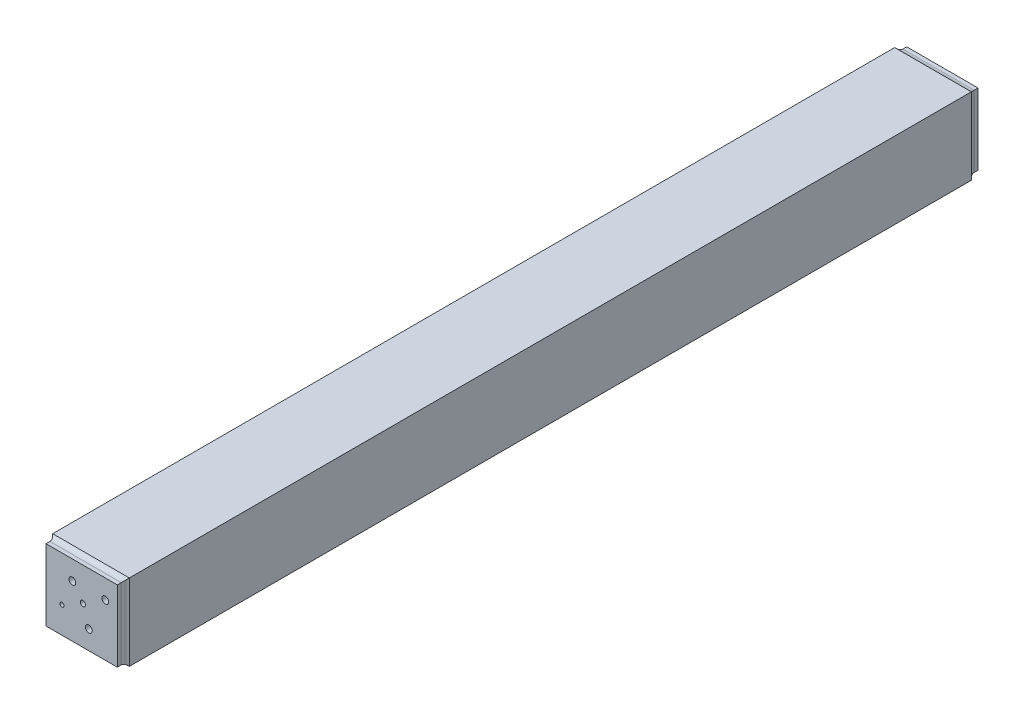
SolidWorks part; units mm, degrees
material "1060 Alloy"
ref_plane "Front Plane" through (0, 0, 0) normal (0, 0, 1) x (1, 0, 0)
ref_plane "Top Plane" through (0, 0, 0) normal (0, 1, 0) x (1, 0, 0)
ref_plane "Right Plane" through (0, 0, 0) normal (1, 0, 0) x (0, 0, -1)
sketch "Sketch1" plane through (0, 0, 0) normal (0, 0, 1) x (1, 0, 0)
  line L0 (22.265, 0) -> (22.265, -44.53) construction
  line L1 (0, 0) -> (44.53, 0) construction
  line L2 (0, 0) -> (0, -44.53) construction
  line L3 (0, -44.53) -> (44.53, -44.53) construction
  line L4 (44.53, 0) -> (44.53, -44.53) construction
  line L5 (42.98, -1.55) -> (1.55, -1.55)
  line L6 (42.98, -1.55) -> (42.98, -42.98)
  line L7 (42.98, -42.98) -> (1.55, -42.98)
  line L8 (1.55, -1.55) -> (1.55, -42.98)
  line L9 (44.53, -22.265) -> (0, -22.265) construction
  line L10 (31.93, -10.9) -> (31.93, 0) construction
  line L11 (31.93, -12.9) -> (12.93, -12.9) construction
  line L12 (33.93, -12.9) -> (44.53, -12.9) construction
  circle A0 centre (12.93, -12.9) radius 2
  circle A1 centre (31.93, -12.9) radius 2
  circle A2 centre (12.93, -12.9) radius 2.6 construction
  dimension "D2" = 4
  dimension "D1" = 44.53
  dimension "D3" = 41.43
  dimension "D4" = 10.9
  dimension "D5" = 10.6
extrude "Boss-Extrude1" add sketch "Sketch1" against normal blind 5.42
sketch "Sketch2" plane through (0, 0, 0) normal (0, 0, -1) x (-1, 0, 0)
  line L0 (0, 0) -> (-44.53, 0) construction
  line L1 (-3.175, -3.175) -> (-41.355, -3.175)
  line L2 (-3.175, -3.175) -> (-3.175, -41.355)
  line L3 (-3.175, -41.355) -> (-41.355, -41.355)
  line L4 (-41.355, -3.175) -> (-41.355, -41.355)
  line L5 (0, 0) -> (-44.53, 0)
  line L6 (0, 0) -> (0, -44.53)
  line L7 (0, -44.53) -> (-44.53, -44.53)
  line L8 (-44.53, 0) -> (-44.53, -44.53)
  line L9 (0, -44.53) -> (-44.53, -44.53) construction
  line L10 (-44.53, 0) -> (-44.53, -44.53) construction
  line L11 (0, 0) -> (0, -44.53) construction
  line L13 (-22.265, -41.355) -> (-22.265, -44.53) construction
  line L14 (-41.355, -22.265) -> (-44.53, -22.265) construction
  line L15 (-22.265, -3.175) -> (-22.265, 0) construction
  line L16 (-3.175, -22.265) -> (0, -22.265) construction
  dimension "D1" = 3.175
extrude "Boss-Extrude2" add sketch "Sketch2" against normal blind 489.16
sketch "Sketch3" plane through (0, 0, 489.16) normal (0, 0, 1) x (1, 0, 0)
  line L0 (22.265, -1.55) -> (22.265, -42.98) construction
  line L1 (1.55, -1.55) -> (42.98, -1.55)
  line L2 (1.55, -1.55) -> (1.55, -42.98)
  line L3 (1.55, -42.98) -> (42.98, -42.98)
  line L4 (42.98, -1.55) -> (42.98, -42.98)
  line L5 (1.55, -22.265) -> (42.98, -22.265) construction
  line L6 (22.265, 0) -> (22.265, -44.53) construction
  line L7 (44.53, -22.265) -> (0, -22.265) construction
  line L8 (42.98, -1.55) -> (1.55, -1.55) construction
  circle A0 centre (16.84, -12.6755) radius 2
  circle A1 centre (36.01, -12.6755) radius 2
  circle A2 centre (26.425, -32.01) radius 2
  circle A3 centre (22.9728, -20.927) radius 1.505
  circle A4 centre (10.8715, -27.5658) radius 1.2
  circle A5 centre (31.93, -12.9) radius 2 construction
  dimension "D1" = 3.01
  dimension "D2" = 2.4
extrude "Boss-Extrude3" add sketch "Sketch3" along normal blind 5.42
fillet "Fillet1" radius 4 8 edges at (22.265, -42.98, 489.16) (42.98, -22.265, 489.16) (1.55, -22.265, 489.16) (22.265, -1.55, 489.16) (1.55, -22.265, 0) (22.265, -42.98, 0) (42.98, -22.265, 0) (22.265, -1.55, 0)
ref_axis "Axis1" through (31.93, -12.9, -5.42) along (0, 0, 1)
